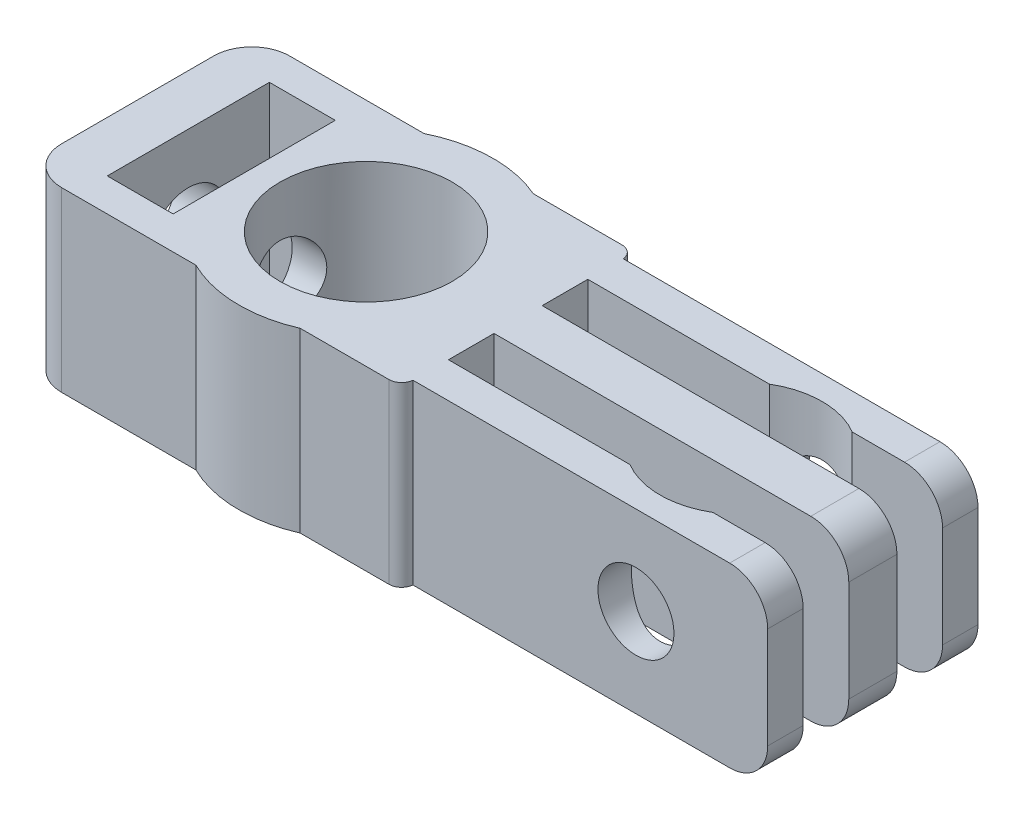
SolidWorks part; units mm, degrees
ref_plane "Front Plane" through (0, 0, 0) normal (0, 0, 1) x (1, 0, 0)
ref_plane "Top Plane" through (0, 0, 0) normal (0, 1, 0) x (1, 0, 0)
ref_plane "Right Plane" through (0, 0, 0) normal (1, 0, 0) x (0, 0, -1)
sketch "Sketch1" plane through (0, 0, 0) normal (0, 1, 0) x (1, 0, 0)
  line L1 (-2.54, -5.842) -> (2.54, -5.842)
  line L2 (-2.54, -5.842) -> (-2.54, 5.842)
  line L3 (-2.54, 5.842) -> (2.54, 5.842)
  line L4 (2.54, -5.842) -> (2.54, 5.842)
  line L5 (-2.54, -5.842) -> (2.54, 5.842) construction
  line L6 (-2.54, 5.842) -> (2.54, -5.842) construction
  point P0 (0, 0)
  dimension "D1" = 5.08
  dimension "D2" = 11.684
extrude "Boss-Extrude1" add sketch "Sketch1" along normal blind 8.89 contours L2 L1 L4 L3
sketch "Sketch2" plane through (0, 8.89, 0) normal (0, 1, 0) x (1, 0, 0)
  line L0 (-2.54, -5.842) -> (-2.54, 5.842) construction
  circle A0 centre (-5.08, 0) radius 4.318
  dimension "D1" = 8.636
  dimension "D2" = 2.54
extrude "Cut-Extrude1" cut sketch "Sketch2" against normal up to surface (8.89 mm away) up to face at (0, 0, 0)
sketch "Sketch7" plane through (0, 0, 0) normal (0, -1, 0) x (1, 0, 0)
  line L0 (-2.54, 3.4919) -> (-2.54, 5.842)
  line L1 (-2.54, -3.4919) -> (-2.54, -5.842)
  arc A0 (-2.54, 3.4919) -> (-2.54, -3.4919) centre (-5.08, 0) ccw
  arc A1 (-2.54, 5.842) -> (-2.54, -5.842) centre (-5.08, 0) ccw
extrude "Boss-Extrude4" add sketch "Sketch7" against normal up to surface (8.89 mm away) up to face at (-0.5503, 8.89, 0)
sketch "Sketch8" plane through (0, 0, 0) normal (0, -1, 0) x (1, 0, 0)
  line L0 (-7.8941, 5.715) -> (-16.5303, 5.715)
  line L1 (-16.5303, 5.715) -> (-16.5303, -5.715)
  line L2 (-16.5303, -5.715) -> (-7.8941, -5.715)
  arc A0 (-2.54, 5.842) -> (-2.54, -5.842) centre (-5.08, 0) ccw construction
  arc A1 (-7.8941, 5.715) -> (-7.8941, -5.715) centre (-5.08, 0) ccw
  dimension "D1" = 11.43
  dimension "D2" = 5.08
extrude "Boss-Extrude5" add sketch "Sketch8" against normal up to surface (8.89 mm away) up to face at (-5.08, 8.89, 4.318)
sketch "Sketch9" plane through (0, 0, 0) normal (0, -1, 0) x (1, 0, 0)
  line L0 (-16.5303, 5.715) -> (-16.5303, -5.715) construction
  line L1 (-13.9903, 4.064) -> (-10.6883, 4.064)
  line L2 (-13.9903, 4.064) -> (-13.9903, -4.064)
  line L3 (-13.9903, -4.064) -> (-10.6883, -4.064)
  line L4 (-10.6883, 4.064) -> (-10.6883, -4.064)
  line L5 (-13.9903, 4.064) -> (-10.6883, -4.064) construction
  line L6 (-13.9903, -4.064) -> (-10.6883, 4.064) construction
  point P0 (-12.3393, 0)
  point P5 (0, 0)
  point P7 (-12.8439, 0)
  dimension "D1" = 8.128
  dimension "D2" = 3.302
  dimension "D3" = 2.54
extrude "Cut-Extrude4" cut sketch "Sketch9" against normal up to surface (8.89 mm away) up to face at (-5.08, 8.89, 4.318)
sketch "Sketch10" plane through (-16.5303, 0, 0) normal (-1, 0, 0) x (0, 0, 1)
  line L0 (0, 8.89) -> (0, 0) construction
  line L1 (5.715, 8.89) -> (-5.715, 8.89) construction
  circle A0 centre (0, 4.445) radius 1.905
  point P2 (0, 6.7969)
  point P8 (0, 4.445)
  dimension "D1" = 3.81
extrude "Cut-Extrude5" cut sketch "Sketch10" against normal up to surface (7.5752 mm away) up to face at (-5.08, 8.89, 4.318)
sketch "Sketch11" plane through (2.54, 0, 0) normal (1, 0, 0) x (0, 0, -1)
  line L0 (-5.842, 8.89) -> (5.842, 8.89) construction
  line L1 (-1.2065, 8.89) -> (1.2065, 8.89)
  line L2 (-1.2065, 8.89) -> (-1.2065, 0)
  line L3 (-1.2065, 0) -> (1.2065, 0)
  line L4 (1.2065, 8.89) -> (1.2065, 0)
  line L5 (-5.842, 0) -> (5.842, 0) construction
  line L7 (5.2705, 8.89) -> (3.4925, 8.89)
  line L8 (5.2705, 8.89) -> (5.2705, 0)
  line L9 (5.2705, 0) -> (3.4925, 0)
  line L10 (3.4925, 8.89) -> (3.4925, 0)
  line L11 (-5.2705, 8.89) -> (-3.4925, 8.89)
  line L12 (-5.2705, 8.89) -> (-5.2705, 0)
  line L13 (-5.2705, 0) -> (-3.4925, 0)
  line L14 (-3.4925, 8.89) -> (-3.4925, 0)
  point P16 (0, 0)
  dimension "D1" = 2.413
  dimension "D2" = 2.286
  dimension "D3" = 2.286
  dimension "D4" = 1.778
extrude "Boss-Extrude6" add sketch "Sketch11" along normal blind 17.78
sketch "Sketch12" plane through (0, 0, 5.2705) normal (0, 0, 1) x (1, 0, 0)
  line L0 (20.32, 8.89) -> (20.32, 0) construction
  line L1 (20.32, 8.89) -> (20.32, 0) construction
  circle A0 centre (13.716, 4.445) radius 1.905
  point P8 (20.32, 4.445)
  dimension "D2" = 3.81
  dimension "D1" = 6.604
extrude "Cut-Extrude6" cut sketch "Sketch12" against normal up to surface (10.541 mm away) up to face at (11.43, 4.445, -5.2705)
sketch "Sketch13" plane through (0, 8.89, 0) normal (0, 1, 0) x (1, 0, 0)
  line L0 (11.811, -5.2705) -> (15.621, -5.2705) construction
  line L1 (13.716, -5.2705) -> (13.716, 5.2705) construction
  line L2 (20.32, 5.2705) -> (2.54, 5.2705) construction
  line L3 (11.6379, 3.4925) -> (15.7941, 3.4925)
  line L4 (20.32, 3.4925) -> (2.54, 3.4925) construction
  line L5 (11.6379, -3.4925) -> (15.7941, -3.4925)
  line L6 (20.32, -3.4925) -> (2.54, -3.4925) construction
  arc A0 (11.6379, -3.4925) -> (15.7941, -3.4925) centre (13.716, 0) ccw
  arc A1 (15.7941, 3.4925) -> (11.6379, 3.4925) centre (13.716, 0) ccw
  point P19 (0, 0)
  point P20 (15.7941, 3.4925)
  point P21 (11.811, 3.4925)
  point P22 (0, 0)
  dimension "D1" = 8.128
extrude "Cut-Extrude7" cut sketch "Sketch13" against normal up to surface (8.89 mm away) up to face at (-12.3393, 0, 0)
fillet "Fillet3" radius 0.635 2 edges at (2.54, 4.445, -5.842) (2.54, 4.445, 5.842)
fillet "Fillet4" radius 1.905 8 edges at (-16.5303, 4.445, -5.715) (-16.5303, 4.445, 5.715) (20.32, 0, 4.3815) (20.32, 0, 0) (20.32, 0, -4.3815) (20.32, 8.89, -4.3815) (20.32, 8.89, 0) (20.32, 8.89, 4.3815)
